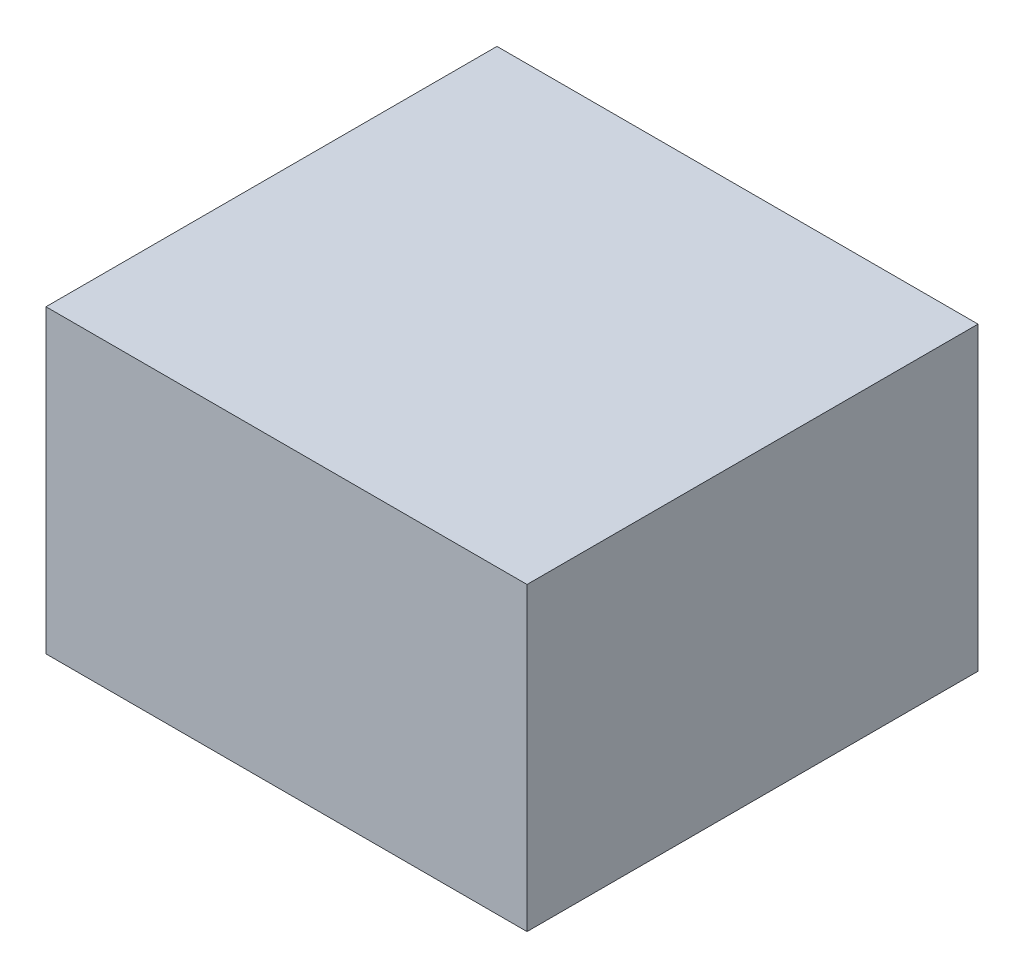
SolidWorks part; units mm, degrees
material "Rubber"
ref_plane "Front Plane" through (0, 0, 0) normal (0, 0, 1) x (1, 0, 0)
ref_plane "Top Plane" through (0, 0, 0) normal (0, 1, 0) x (1, 0, 0)
ref_plane "Right Plane" through (0, 0, 0) normal (1, 0, 0) x (0, 0, -1)
sketch "Sketch1" plane through (0, 0, 0) normal (0, 1, 0) x (1, 0, 0)
  line L1 (0, 0) -> (16, 0)
  line L2 (0, 0) -> (0, -15)
  line L3 (0, -15) -> (16, -15)
  line L4 (16, 0) -> (16, -15)
  dimension "D1" = 15
  dimension "D2" = 16
extrude "Boss-Extrude1" add sketch "Sketch1" along normal blind 10
